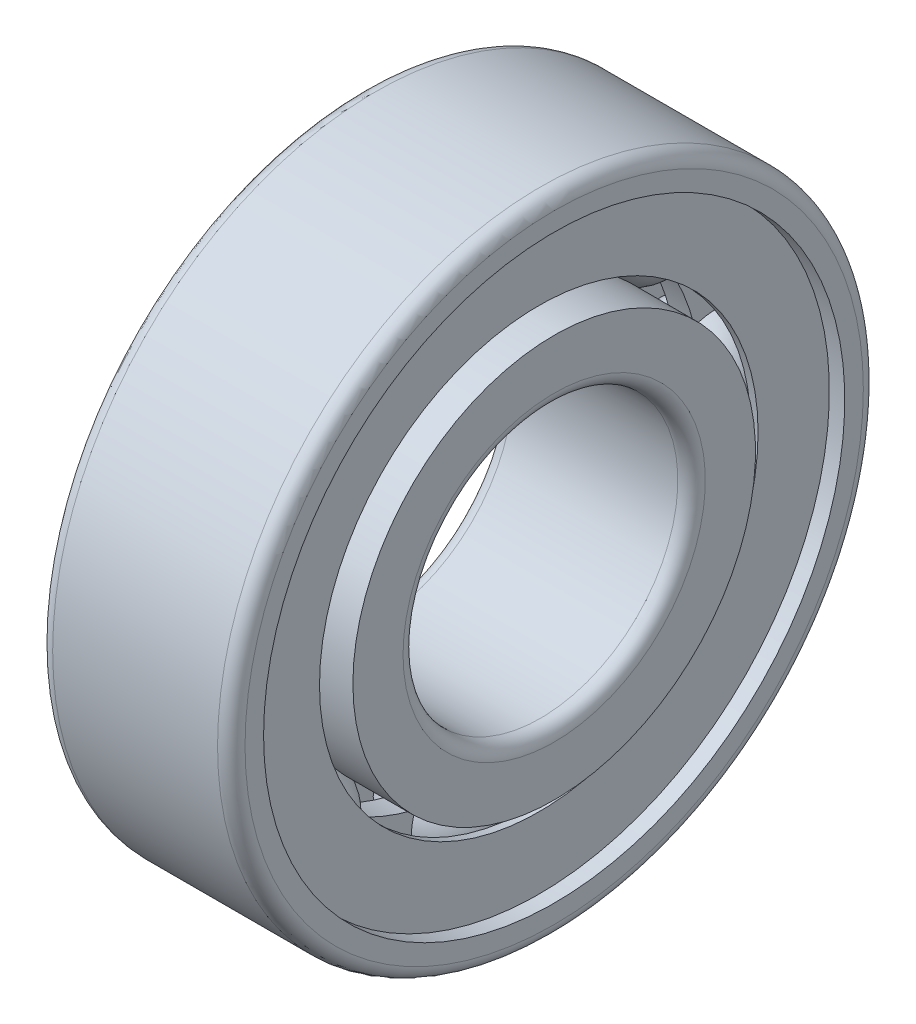
SolidWorks part; units mm, degrees
revolve "凸台-旋转2" add sketch "草图6" angle 360 about L4
sketch "草图6" plane through (0, 0, 0) normal (0, 0, 1) x (1, 0, 0)
  line L0 (0, 0) -> (5.5439, 0) construction
  line L1 (-12.4206, 0) -> (9.8128, 0) construction
  line L2 (0, 0) -> (0, 11.4011) construction
  line L3 (-5.5681, 17.9) -> (6.1049, 17.9) construction
  line L4 (-5.5681, 17.9) -> (6.1049, 17.9) construction
  line L5 (-3.969, 17.9) -> (3.969, 17.9)
  arc A0 (-3.969, 17.9) -> (3.969, 17.9) centre (0, 17.9) ccw
  dimension "Dw" = 7.938
revolve "基体-旋转" add sketch "草图2" angle 360 about L0
sketch "草图2" plane through (0, 0, 0) normal (0, 0, 1) x (1, 0, 0)
  line L0 (-12.4206, 0) -> (9.8128, 0) construction
  line L1 (0, 0) -> (0, 37.3563) construction
  line L2 (-5.5681, 17.9) -> (6.1049, 17.9) construction
  line L3 (-0.8732, 18.9915) -> (0.8732, 18.9915)
  line L4 (-0.8732, 18.9915) -> (-0.8732, 16.8085)
  line L5 (-0.8732, 16.8085) -> (0.8732, 16.8085)
  line L6 (0.8732, 18.9915) -> (0.8732, 16.8085)
  dimension "D1" = 1.7464
  dimension "D2" = 0.8732
  dimension "D3" = 2.1829
  dimension "D4" = 1.0915
  dimension "D5" = 17.9
revolve "凸台-旋转1" add sketch "草图3" angle 360 about L1
sketch "草图3" plane through (0, 0, 0) normal (0, 0, 1) x (1, 0, 0)
  line L0 (-5.5681, 17.9) -> (6.1049, 17.9) construction
  line L1 (-5.5681, 17.9) -> (6.1049, 17.9) construction
  line L2 (-12.4206, 0) -> (9.8128, 0) construction
  line L3 (-12.4206, 0) -> (9.8128, 0) construction
  line L4 (0, 0) -> (0, 37.3563) construction
  line L5 (0, 0) -> (0, 37.3563) construction
  line L6 (-4.3659, 17.9) -> (4.3659, 17.9)
  arc A0 (-4.3659, 17.9) -> (4.3659, 17.9) centre (0, 17.9) ccw
  dimension "Dwww" = 8.7318
  dimension "D2" = 4.3659
pattern_circular "阵列(圆周)1" count 8 over 360 about axis through (-12.4206, 0, 0) along (1, 0, 0) of "凸台-旋转1"
revolve "凸台-旋转3" add sketch "草图7" angle 360 about L0
sketch "草图7" plane through (0, 0, 0) normal (0, 0, 1) x (1, 0, 0)
  line L0 (0, 0) -> (6.6488, 0) construction
  line L1 (0, 0) -> (0, 16.8954) construction
  line L2 (-6, 23.5) -> (6, 23.5)
  line L3 (-7, 22.5) -> (-7, 21.15)
  line L4 (-7, 21.15) -> (-2.2608, 21.15)
  line L5 (7, 22.5) -> (7, 21.15)
  line L6 (2.2608, 21.15) -> (5.3448, 21.15)
  line L7 (5.88, 21.15) -> (7, 21.15)
  line L8 (5.3448, 20.8) -> (5.88, 20.8)
  line L9 (5.3448, 20.8) -> (5.3448, 21.15)
  line L11 (5.88, 20.8) -> (5.88, 21.15)
  arc A0 (-6, 23.5) -> (-7, 22.5) centre (-6, 22.5) ccw
  arc A1 (6, 23.5) -> (7, 22.5) centre (6, 22.5) cw
  arc A2 (3.816, 18.9915) -> (-3.816, 18.9915) centre (0, 17.9) ccw construction
  arc A3 (2.2783, 21.15) -> (0, 13.931) centre (0, 17.9) ccw construction
  arc A4 (2.2608, 21.15) -> (-2.2608, 21.15) centre (0, 17.9) ccw
  point P10 (-7, 23.5)
  point P13 (7, 23.5)
  dimension "D3" = 7
  dimension "D4" = 0.5352
  dimension "D5" = 41.6
  dimension "D6" = 1.12
  dimension "B" = 14
ref_plane "基准面1" through (0, 0, 0) normal (0, 0, 1) x (1, 0, 0)
ref_plane "基准面2" through (0, 0, 0) normal (0, 1, 0) x (1, 0, 0)
ref_plane "基准面3" through (0, 0, 0) normal (1, 0, 0) x (0, 0, -1)
sketch "尺寸草图" plane through (0, 0, 0) normal (0, 0, 1) x (1, 0, 0)
  point P0 (0, -75.4307)
  point P1 (7.938, -75.4307)
  point P2 (0, 50.7088)
  point P3 (20, 50.7088)
  point P4 (47, 50.7088)
  point P5 (14, 50.7088)
  point P6 (0, -10.9899)
  point P7 (29.3, -10.9899)
  point P8 (41.6, -10.9899)
  point P9 (1, -10.9899)
  point P10 (8, -75.4307)
  dimension "B" = 14
sketch "草图4" plane through (0, 0, 0) normal (0, 0, 1) x (1, 0, 0)
  line L0 (0, 0) -> (8.1272, 0) construction
  line L1 (-12.4206, 0) -> (9.8128, 0) construction
  line L3 (-0.8732, 18.9915) -> (0.8732, 18.9915) construction
  line L4 (-4.3659, 23.3574) -> (4.3659, 23.3574)
  line L5 (-4.3659, 23.3574) -> (-4.3659, 18.9915)
  line L6 (-4.3659, 18.9915) -> (4.3659, 18.9915)
  line L7 (4.3659, 23.3574) -> (4.3659, 18.9915)
revolve "切除-旋转1" cut sketch "草图4" angle 360 about L0
sketch "草图5" plane through (0, 0, 0) normal (0, 0, 1) x (1, 0, 0)
  line L0 (0, 0) -> (8.2665, 0) construction
  line L1 (-12.4206, 0) -> (9.8128, 0) construction
  line L2 (-0.8732, 16.8085) -> (0.8732, 16.8085) construction
  line L3 (-4.3659, 16.8085) -> (4.3659, 16.8085)
  line L4 (-4.3659, 16.8085) -> (-4.3659, 12.4426)
  line L5 (-4.3659, 12.4426) -> (4.3659, 12.4426)
  line L6 (4.3659, 16.8085) -> (4.3659, 12.4426)
revolve "切除-旋转2" cut sketch "草图5" angle 360 about L0
pattern_circular "阵列(圆周)2" count 8 over 360 about axis through (-12.4206, 0, 0) along (1, 0, 0) of "凸台-旋转2"
sketch "草图8" plane through (0, 0, 0) normal (0, 0, 1) x (1, 0, 0)
  line L0 (-12.4206, 0) -> (9.8128, 0) construction
  line L1 (-12.4206, 0) -> (9.8128, 0) construction
  line L2 (7, 22.5) -> (7, 21.15) construction
  line L3 (-7, 14.65) -> (-2.2608, 14.65)
  line L4 (-7, 14.65) -> (-7, 11)
  line L5 (-6, 10) -> (6, 10)
  line L6 (7, 14.65) -> (7, 11)
  line L7 (-7, 22.5) -> (-7, 21.15) construction
  line L8 (2.2608, 14.65) -> (7, 14.65)
  arc A0 (-7, 11) -> (-6, 10) centre (-6, 11) ccw
  arc A1 (6, 10) -> (7, 11) centre (6, 11) ccw
  arc A2 (-3.816, 16.8085) -> (3.816, 16.8085) centre (0, 17.9) ccw construction
  arc A3 (-3.816, 16.8085) -> (3.816, 16.8085) centre (0, 17.9) ccw construction
  arc A4 (-2.2608, 14.65) -> (2.2608, 14.65) centre (0, 17.9) ccw
  dimension "D1" = 1
  dimension "DD" = 20
  dimension "D2" = 0.01
revolve "凸台-旋转4" add sketch "草图8" angle 360 about L1
sketch "草图10" plane through (0, 0, 0) normal (0, 0, 1) x (1, 0, 0)
  line L0 (5.3448, 21.15) -> (5.3448, -21.15) construction
  line L1 (5.88, 20.8) -> (5.3448, 20.8)
  line L2 (5.88, 20.8) -> (5.88, 15.9598)
  line L3 (5.88, 15.9598) -> (5.3448, 15.9598)
  line L4 (5.3448, 20.8) -> (5.3448, 15.9598)
  line L5 (2.2608, 14.65) -> (7, 14.65) construction
  line L6 (0, 0) -> (-5.3515, 0) construction
  line L7 (-12.4206, 0) -> (9.8128, 0) construction
  dimension "D1" = 1.3098
revolve "凸台-旋转5" add sketch "草图10" angle 360 about L6
sketch "草图11" plane through (0, 0, 0) normal (1, 0, 0) x (0, 0, -1)
  circle A0 centre (0, 0) radius 23.5
  circle A1 centre (0, 0) radius 23.5 construction
extrude "切除-拉伸1" cut sketch "草图11" against normal blind 10
mirror "镜向所有1" about plane through (0, 0, 0) normal (1, 0, 0) of bodies 109
equation "\"D5@草图7\" = \"防尘圈径D3@尺寸草图\""
equation "\"Z@阵列(圆周)1\"=\"球数Z@尺寸草图\" "
equation "\"Dw@草图6\"=\"球径DW@尺寸草图\""
equation "\"DD@草图8\"=\"d@尺寸草图\""
equation "\"D@草图7\"=\"DD@尺寸草图\""
equation "\"B@草图7\"=\"B@尺寸草图\" "
equation "\"DD2@草图8\"=\"内圈外径DD2@尺寸草图\""
equation "\"R@草图7\"=\"r@尺寸草图\""
equation "\"D3@草图2\" = 0.25*\"Dwww@草图3\""
equation "\"D4@草图2\" = \"D3@草图2\"/2"
equation "\"Dwww@草图3\" = 1.1*\"Dw@草图6\""
equation "\"D2@草图3\" = 0.5*\"Dwww@草图3\""
equation "\"D1@草图2\" = 0.2*\"Dwww@草图3\""
equation "\"D2@草图2\" = 0.5*\"D1@草图2\""
equation "\"切除位置@草图4\" = \"Dwww@草图3\"/2"
equation "\"D1@阵列(圆周)2\" = \"Z@阵列(圆周)1\""
equation "\"D3@草图7\" = \"B@草图7\" / 2"
equation "\"D1@草图8\" = \"R@草图7\""
equation "\"D2@草图7\" = 0.9*\"D@草图7\""
equation "\"D5@草图2\" = 0.25* ( \"D2@草图7\" + \"DD2@草图8\" )  "
equation "\"D6@草图7\" = 0.08 * \"B@草图7\""
equation "\"D1@草图10\" = 0.15*\"Dwww@草图3\""
